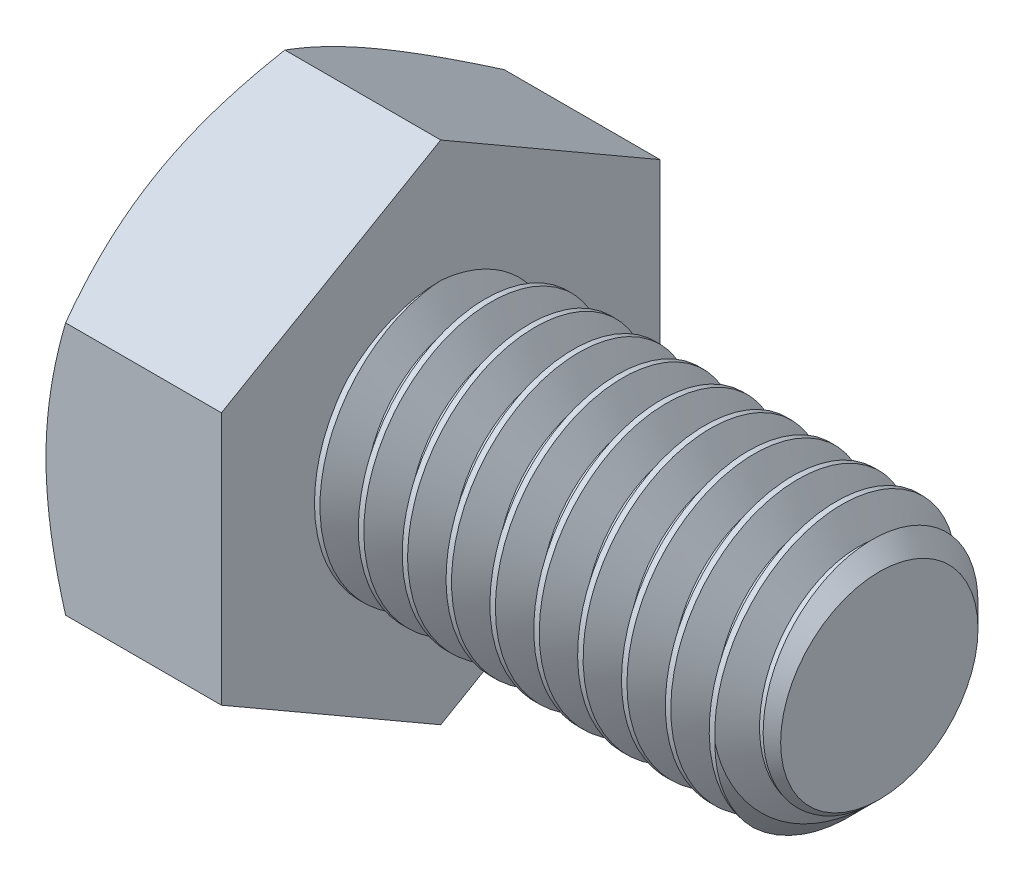
SolidWorks part; units mm, degrees
ref_plane "Front Plane" through (0, 0, 0) normal (0, 0, 1) x (1, 0, 0)
ref_plane "Top Plane" through (0, 0, 0) normal (0, 1, 0) x (1, 0, 0)
ref_plane "Right Plane" through (0, 0, 0) normal (1, 0, 0) x (0, 0, -1)
sketch "Sketch1" plane through (0, 0, 0) normal (0, 0, 1) x (1, 0, 0)
  line L0 (-7, 0) -> (7, 0) construction
  line L1 (-3, 5) -> (-3, -5) construction
  line L2 (-7, 5) -> (-7, -5) construction
  line L3 (7, 3) -> (7, -3) construction
  point P8 (3.5, -3)
  dimension "D1" = 3.5
  dimension "Thread Dia" = 6
  dimension "Hex" = 10
  dimension "Head Ht" = 4
  dimension "Length" = 10
ref_plane "Plane2" through (7, 0, 0) normal (1, 0, 0) x (0, 0, -1)
sketch "Sketch2" plane through (7, 0, 0) normal (1, 0, 0) x (0, 0, -1)
  circle A0 centre (0, 0) radius 3
extrude "Boss-Extrude1" add sketch "Sketch2" against normal up to vertex (10 mm away) up to point (-3, -5, 0)
sketch "Sketch4" plane through (7, 0, 0) normal (1, 0, 0) x (0, 0, -1)
  circle A1 centre (0, 0) radius 3
  circle A2 centre (0, 0) radius 3
  dimension "D1" = 0
curve "Helix/Spiral1" pitch 1 height 11 turns 11 parameters "Pitch"=1
chamfer "Chamfer1" distance 0.75 angle 45 1 edges at (7, 0, -3)
sketch "Sketch5" plane through (0, 0, 0) normal (0, 0, 1) x (1, 0, 0)
  line L0 (7, 3) -> (7.375, 2.3505)
  line L1 (7.375, 2.3505) -> (7.5, 2.3505)
  line L2 (7.5, 2.3505) -> (7.875, 3)
  line L3 (7, 3) -> (7.875, 3)
  line L4 (7.4375, 2.3505) -> (7.4375, 3) construction
  line L5 (7.1875, 2.6752) -> (7.6875, 2.6752) construction
  line L6 (7, -3) -> (7, 3) construction
  dimension "D1" = 60
  dimension "D2" = 0.125
  dimension "D3" = 0.5
sweep "Cut-Sweep1" cut profiles "Sketch5" path "Helix/Spiral1" align with end faces yes
sketch "Sketch3" plane through (-3, 0, 0) normal (-1, 0, 0) x (0, 0, 1)
  line L0 (0, 5) -> (0, -5) construction
  line L1 (-5, -2.8868) -> (0, -5.7735)
  line L2 (0, -5.7735) -> (5, -2.8868)
  line L3 (5, -2.8868) -> (5, 2.8868)
  line L4 (5, 2.8868) -> (0, 5.7735)
  line L5 (0, 5.7735) -> (-5, 2.8868)
  line L6 (-5, 2.8868) -> (-5, -2.8868)
  circle A0 centre (0, 0) radius 5 construction
extrude "Boss-Extrude2" add sketch "Sketch3" along normal up to vertex (4 mm away) up to point (-7, -5, 0)
sketch "Sketch6" plane through (-7, 0, 0) normal (-1, 0, 0) x (0, 0, 1)
  circle A0 centre (0, 0) radius 5 construction
  circle A1 centre (0, 0) radius 5
extrude "Cut-Extrude1" cut sketch "Sketch6" against normal through all draft 60 flip side to cut
sketch "Sketch7" plane through (-7, 0, 0) normal (-1, 0, 0) x (0, 0, 1)
  line L0 (0, 0) -> (0, 5) construction
  line L2 (0, 5) -> (0, -5) construction
  line L3 (-4.3301, 2.5) -> (4.3301, 2.5) construction
  circle A1 centre (0, 0) radius 5 construction
  text T0 "10.9" font "Arial" height in points 6
  point P8 (0, 2.5)
extrude "Cut-Extrude2" cut sketch "Sketch7" against normal blind 0.25
sketch "Sketch9" plane through (0, 0, 0) normal (0, 0, 1) x (1, 0, 0)
  line L0 (-3, 3) -> (-3, 0)
  line L1 (-3, 0) -> (-44, 0)
  line L2 (-44, 0) -> (-47, 3)
  line L3 (-47, 3) -> (-3, 3)
  line L4 (-7, 0) -> (7, 0) construction
  line L5 (-3, 5) -> (-3, -5) construction
  line L6 (7, 3) -> (7, -3) construction
  dimension "D1" = 45
  dimension "MinThreadLg" = 54
revolve "Revolve1" [suppressed] add sketch "Sketch9" angle 360 about L1
equation "\"D2@Sketch5\" = \"Pitch@Helix/Spiral1\"*.125"
equation "\"D3@Sketch5\" = \"Pitch@Helix/Spiral1\"*.50"
equation "\"D3@Helix/Spiral1\" = \"Length@Sketch1\"+\"Pitch@Helix/Spiral1\""
equation "\"D1@Chamfer1\" = \"Pitch@Helix/Spiral1\"*.750"
equation "\"D1@Sketch1\" = \"Pitch@Helix/Spiral1\"*3.50"
